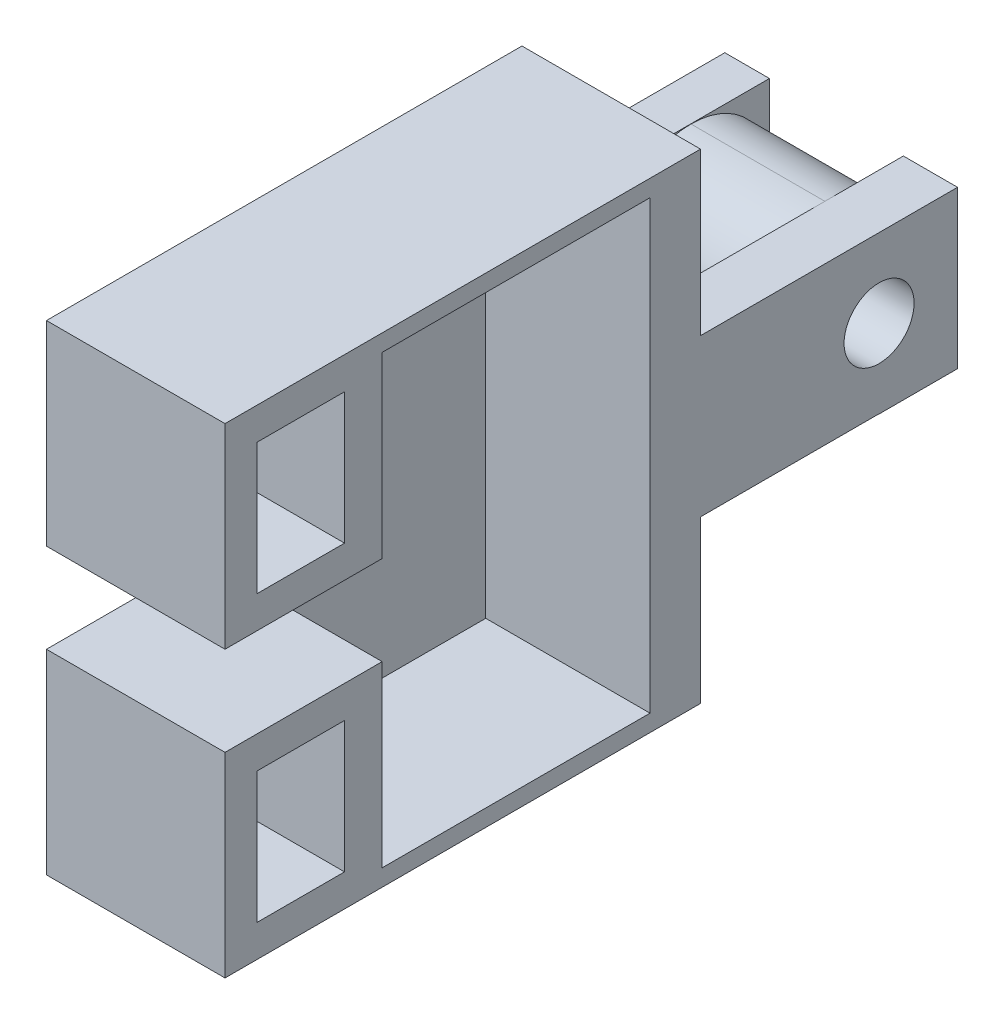
SolidWorks part; units mm, degrees
material "6061-T6 (SS)"
ref_plane "Front Plane" through (0, 0, 0) normal (1, 0, 0) x (0, 1, 0)
ref_plane "Top Plane" through (0, 0, 0) normal (0, 0, 1) x (0, 1, 0)
ref_plane "Right Plane" through (0, 0, 0) normal (0, 1, 0) x (-1, 0, 0)
sketch "Sketch1" plane through (0, 0, 0) normal (1, 0, 0) x (0, 1, 0)
  line L3 (0, 0) -> (0, 25.4)
  line L4 (0, 25.4) -> (22.3256, 25.4)
  line L5 (22.3256, 0) -> (22.3256, 25.4)
  arc A1 (0, 0) -> (22.3256, 0) centre (11.1628, 0) ccw
  dimension "D1" = 25.4
  dimension "D2" = 22.3256
extrude "Feature B" add sketch "Sketch1" along normal blind 7.7061
sketch "Sketch3" plane through (0, 0, 0) normal (-1, 0, 0) x (0, -1, 0)
  circle A0 centre (-11.1628, 0) radius 11.1628
  point P5 (-11.1628, 0)
extrude "Feature A" add sketch "Sketch3" along normal blind 25.4
sketch "Sketch5" plane through (7.7061, 0, 0) normal (1, 0, 0) x (0, 1, 0)
  line L0 (0, 25.4) -> (0, 0) construction
  line L1 (-21.7161, 25.4) -> (44.0417, 25.4)
  line L2 (-21.7161, 25.4) -> (-21.7161, 32.5842)
  line L3 (-21.7161, 32.5842) -> (44.0417, 32.5842)
  line L4 (44.0417, 25.4) -> (44.0417, 32.5842)
  dimension "D1" = 65.7578
  dimension "D2" = 21.7161
  dimension "D3" = 7.1842
extrude "Feature C" add sketch "Sketch5" against normal blind 25.4
sketch "Sketch6" plane through (0, 0, 32.5842) normal (0, 0, 1) x (1, 0, 0)
  line L0 (-17.6939, 44.0417) -> (-17.6939, -21.7161) construction
  line L1 (7.7061, -21.7161) -> (-17.6939, -21.7161)
  line L2 (7.7061, -21.7161) -> (7.7061, -20.5872)
  line L3 (7.7061, -20.5872) -> (-17.6939, -20.5872)
  line L4 (-17.6939, -21.7161) -> (-17.6939, -20.5872)
  line L5 (7.7061, 44.0417) -> (7.7061, -21.7161) construction
  line L6 (-17.6939, 44.0417) -> (7.7061, 44.0417)
  line L7 (-17.6939, 44.0417) -> (-17.6939, 42.9128)
  line L8 (-17.6939, 42.9128) -> (7.7061, 42.9128)
  line L9 (7.7061, 44.0417) -> (7.7061, 42.9128)
  dimension "D1" = 1.1289
  dimension "D2" = 1.1289
extrude "Feature D" add sketch "Sketch6" along normal blind 38.1
sketch "Sketch8" plane through (0, 0, 70.6842) normal (0, 0, 1) x (1, 0, 0)
  line L0 (7.7061, 42.9128) -> (7.7061, -20.5872) construction
  line L1 (-17.6939, -21.7161) -> (7.7061, -21.7161)
  line L2 (-17.6939, -21.7161) -> (-17.6939, 4.8128)
  line L3 (-17.6939, 4.8128) -> (7.7061, 4.8128)
  line L4 (7.7061, -21.7161) -> (7.7061, 4.8128)
  line L6 (-17.6939, 44.0417) -> (7.7061, 44.0417)
  line L7 (-17.6939, 44.0417) -> (-17.6939, 17.5128)
  line L8 (-17.6939, 17.5128) -> (7.7061, 17.5128)
  line L9 (7.7061, 44.0417) -> (7.7061, 17.5128)
  dimension "D1" = 26.5289
  dimension "D2" = 26.5289
extrude "Boss-Extrude5" add sketch "Sketch8" along normal blind 22.3548
ref_point "Point1"
ref_plane "Plane1" through (0, 0, 0) normal (0, 0, 1) x (0, -1, 0)
split line "Split Line5"
sketch "Sketch35" plane through (0, 44.0417, 0) normal (0, 1, 0) x (-1, 0, 0)
  line L1 (-7.7061, 93.039) -> (17.6939, 93.039)
  line L2 (-7.7061, 93.039) -> (-7.7061, 25.4)
  line L3 (-7.7061, 25.4) -> (17.6939, 25.4)
  line L4 (17.6939, 93.039) -> (17.6939, 25.4)
extrude "Boss-Extrude14" add sketch "Sketch35" along normal blind 1.27
sketch "Sketch36" plane through (0, -21.7161, 0) normal (0, -1, 0) x (1, 0, 0)
  line L1 (-17.6939, 93.039) -> (7.7061, 93.039)
  line L2 (-17.6939, 93.039) -> (-17.6939, 25.4)
  line L3 (-17.6939, 25.4) -> (7.7061, 25.4)
  line L4 (7.7061, 93.039) -> (7.7061, 25.4)
  line L5 (-17.6939, 93.039) -> (7.7061, 93.039)
  line L6 (-17.6939, 93.039) -> (-17.6939, 25.4)
  line L7 (-17.6939, 25.4) -> (7.7061, 25.4)
  line L8 (7.7061, 93.039) -> (7.7061, 25.4)
sketch "Sketch37" plane through (0, -21.7161, 0) normal (0, -1, 0) x (1, 0, 0)
  line L1 (-17.6939, 93.039) -> (7.7061, 93.039)
  line L2 (-17.6939, 93.039) -> (-17.6939, 25.4)
  line L3 (-17.6939, 25.4) -> (7.7061, 25.4)
  line L4 (7.7061, 93.039) -> (7.7061, 25.4)
extrude "Boss-Extrude15" add sketch "Sketch37" along normal blind 1.27
sketch "Sketch42" plane through (-17.6939, 0, 0) normal (-1, 0, 0) x (0, -1, 0)
  line L1 (-42.9128, 70.6842) -> (20.5872, 70.6842)
  line L2 (-42.9128, 70.6842) -> (-42.9128, 32.5842)
  line L3 (-42.9128, 32.5842) -> (20.5872, 32.5842)
  line L4 (20.5872, 70.6842) -> (20.5872, 32.5842)
extrude "Boss-Extrude17" add sketch "Sketch42" against normal blind 2.032
sketch "Sketch47" plane through (-17.6939, 0, 0) normal (-1, 0, 0) x (0, -1, 0)
  line L0 (-45.3117, 25.4) -> (-45.3117, 93.039) construction
  line L1 (-40.7397, 88.467) -> (-22.0848, 88.467)
  line L2 (-40.7397, 88.467) -> (-40.7397, 76.0347)
  line L3 (-40.7397, 76.0347) -> (-22.0848, 76.0347)
  line L4 (-22.0848, 88.467) -> (-22.0848, 76.0347)
  line L5 (-17.5128, 93.039) -> (-17.5128, 70.6842) construction
  line L6 (-45.3117, 93.039) -> (-17.5128, 93.039) construction
  line L7 (-4.8128, 93.039) -> (-4.8128, 70.6842) construction
  line L8 (-0.2408, 88.467) -> (18.4141, 88.467)
  line L9 (-0.2408, 88.467) -> (-0.2408, 76.0347)
  line L10 (-0.2408, 76.0347) -> (18.4141, 76.0347)
  line L11 (18.4141, 88.467) -> (18.4141, 76.0347)
  line L12 (22.9861, 93.039) -> (22.9861, 25.4) construction
  line L14 (-14.9728, 66.5667) -> (-7.3528, 66.5667)
  line L15 (-14.9728, 66.5667) -> (-14.9728, 60.8534)
  line L16 (-14.9728, 60.8534) -> (-7.3528, 60.8534)
  line L17 (-7.3528, 66.5667) -> (-7.3528, 60.8534)
  dimension "D1" = 4.572
  dimension "D2" = 4.572
  dimension "D3" = 4.572
  dimension "D4" = 4.572
  dimension "D5" = 4.572
  dimension "D6" = 2.54
  dimension "D7" = 2.54
extrude "Cut-Extrude8" cut sketch "Sketch47" against normal up to next
sketch "Sketch58" plane through (0, 22.3256, 0) normal (0, 1, 0) x (-1, 0, 0)
  line L0 (-7.7061, -11.1628) -> (25.4, -11.1628) construction
  line L1 (-7.7061, 0) -> (0, 0)
  line L2 (-7.7061, 0) -> (-7.7061, -11.1628)
  line L3 (-7.7061, -11.1628) -> (0, -11.1628)
  line L4 (0, 0) -> (0, -11.1628)
extrude "Boss-Extrude25" add sketch "Sketch58" against normal blind 22.352
sketch "Sketch60" plane through (0, 0, 0) normal (0, -1, 0) x (1, 0, 0)
  line L4 (-17.6939, 25.4) -> (7.7061, 25.4) construction
  line L8 (-17.6939, 25.4) -> (-25.4, 11.176)
  line L10 (0, 11.1628) -> (-25.4, 11.1628) construction
  line L14 (-25.4, -11.1628) -> (0, -11.1628) construction
  line L16 (-25.4, -11.1628) -> (-25.4, 11.176)
  line L17 (-25.4, -11.1628) -> (-19.05, -11.1628)
  line L18 (-19.05, 11.1628) -> (-19.05, -11.1628)
  line L19 (-11.3439, 25.4) -> (-19.05, 11.1628)
  line L20 (-11.3439, 25.4) -> (-17.6939, 25.4)
  dimension "D2" = 6.35
  dimension "D3" = 6.35
extrude "Boss-Extrude27" add sketch "Sketch60" against normal blind 22.352
sketch "Sketch61" plane through (-25.4, 0, 0) normal (-1, 0, 0) x (0, -1, 0)
  circle A0 centre (-11.1628, 0) radius 4.9788
extrude "Cut-Extrude12" cut sketch "Sketch61" against normal up to next
equation "\"Force1\"= 1000"
equation "\"Youngs\"= 10 * 10 ^ 6"
equation "\"yield\"= 3 * 10 ^ 4"
equation "\"l\"= 1in"
equation "\"Safety\"= 4"
equation "\"Z\"= \"Safety\" * \"Force1\" * \"l\" / ( 2 * \"yield\" )"
equation "\"a\"= ( ( 4 * \"Z\" ) / pi ) ^ ( 1 / 3 )"
equation "\"stressmax\"= ( \"Force1\" * \"l\" ) / ( 2 * \"Z\" )"
equation "\"b\"= ( 2 * \"Force1\" ) / ( \"stressmax\" * 2 * \"a\" )"
equation "\"Force2\"= 500"
equation "\"h\"= 2.5"
equation "\"Zc\"= ( \"Safety\" * \"Force1\" * \"l\" ) / ( 4 * \"yield\" )"
equation "\"c\"= ( ( 6 * \"Zc\" ) / ( \"h\" ) ) ^ ( 1 / 2 )"
equation "\"i\"= 1.5"
equation "\"d\"= \"Force2\" / ( \"i\" * \"stressmax\" )"
equation "\"k\"= 1"
equation "\"Ze\"= ( ( \"Force2\" * \"l\" ) / ( 4 * \"stressmax\" ) ) ^ ( 1 / 2 )"
equation "\"e\"= ( ( 6 * \"Ze\" ) / \"l\" ) ^ ( 1 / 2 )"
equation "\"D1@Feature B\" = \"b\""
equation "\"D1@Feature A\" = \"l\""
equation "\"D2@Sketch5\"=((\"l\"*2+\"d\"*2+.5)-\"a\"*2)/2"
equation "\"D1@Sketch5\"=(\"l\"*2)+(\"d\"*2)+.5"
equation "\"D3@Sketch5\"=\"c\""
equation "\"D1@Feature C\" = \"l\""
equation "\"D1@Sketch6\"=\"d\""
equation "\"D2@Sketch6\"=\"d\""
equation "\"D1@Feature D\" = \"i\""
equation "\"D1@Sketch8\"=\"d\"+\"k\""
equation "\"D2@Sketch8\"=\"d\"+\"k\""
equation "\"D1@Boss-Extrude5\"=\"e\""
